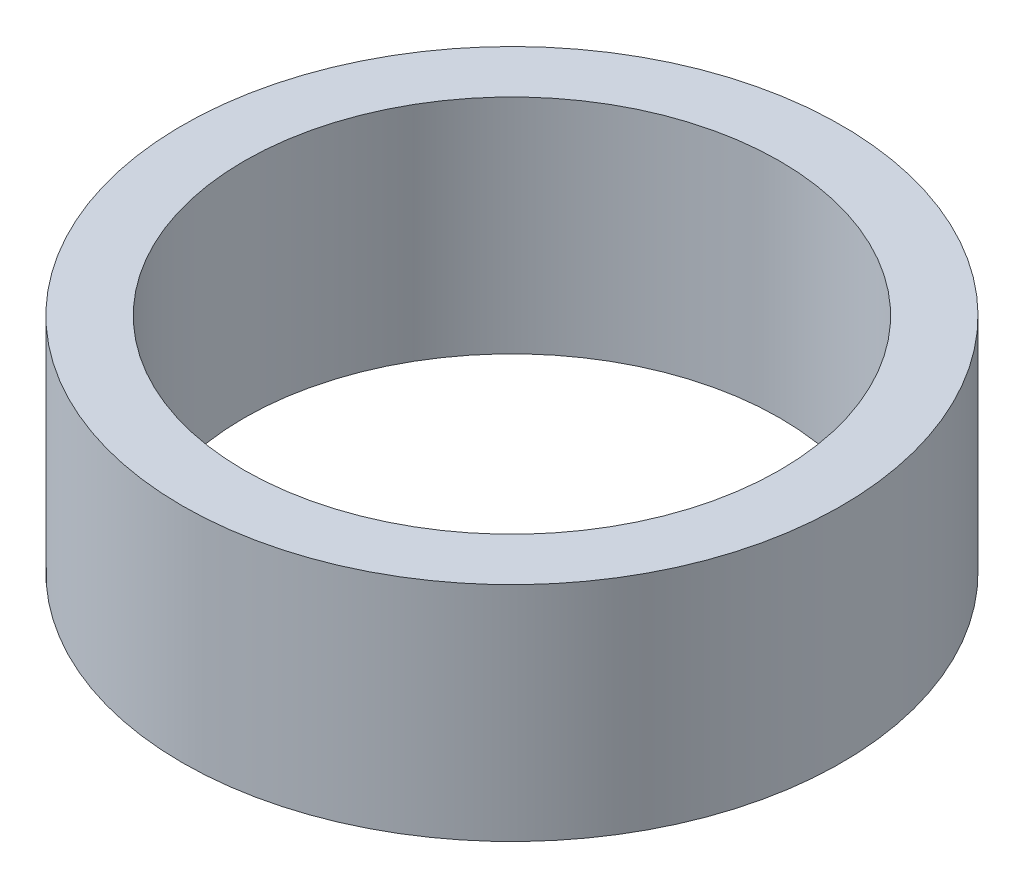
SolidWorks part; units mm, degrees
ref_plane "Front Plane" through (0, 0, 0) normal (0, 0, 1) x (1, 0, 0)
ref_plane "Top Plane" through (0, 0, 0) normal (0, 1, 0) x (1, 0, 0)
ref_plane "Right Plane" through (0, 0, 0) normal (1, 0, 0) x (0, 0, -1)
sketch "Sketch1" plane through (0, 0, 0) normal (0, 1, 0) x (1, 0, 0)
  circle A0 centre (0, 0) radius 40
  dimension "FLANGE_OD" = 80
extrude "Boss-Extrude1" add sketch "Sketch1" along normal blind 27
sketch "Sketch2" plane through (0, 0, 0) normal (0, 1, 0) x (1, 0, 0)
  circle A0 centre (0, 0) radius 32.5
  dimension "BORE_D" = 65
extrude "Cut-Extrude1" cut sketch "Sketch2" along normal through all
sketch "Sketch3" plane through (0, 27, 0) normal (0, 1, 0) x (1, 0, 0)
  circle A0 centre (0, 0) radius 17.5481 construction
  circle A1 centre (-17.5481, 0) radius 1.5
  dimension "BOLT_D" = 3
  dimension "BOLT_PCD" = 35.0961
extrude "Cut-Extrude2" cut sketch "Sketch3" against normal blind 19.9586 rebuild error yes
pattern_circular "CirPattern1" count 4 over 360 rebuild error yes
